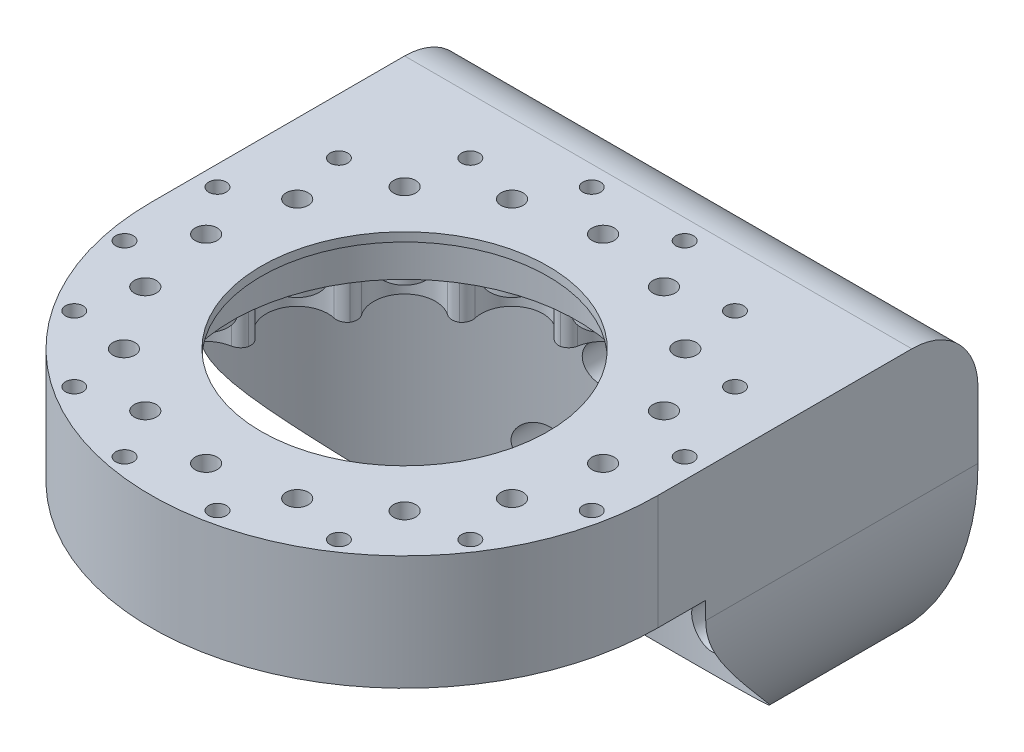
SolidWorks part; units mm, degrees
ref_plane "Front Plane" through (0, 0, 0) normal (0, 0, 1) x (1, 0, 0)
ref_plane "Top Plane" through (0, 0, 0) normal (0, 1, 0) x (1, 0, 0)
ref_plane "Right Plane" through (0, 0, 0) normal (1, 0, 0) x (0, 0, -1)
sketch "Sketch1" plane through (0, 0, 0) normal (0, 1, 0) x (1, 0, 0)
  line L0 (-10.5349, 52.9624) -> (0, 0) construction
  line L1 (0, 0) -> (24.6214, 0) construction
  circle A12 centre (0, 0) radius 39.1
  circle A13 centre (0, 0) radius 57.5
  circle A14 centre (0, 0) radius 54 construction
  circle A15 centre (-10.5349, 52.9624) radius 2
  circle A16 centre (10.5349, 52.9624) radius 2
  circle A17 centre (30.0008, 44.8994) radius 2
  circle A18 centre (44.8994, 30.0008) radius 2
  circle A19 centre (52.9624, 10.5349) radius 2
  circle A20 centre (52.9624, -10.5349) radius 2
  circle A21 centre (44.8994, -30.0008) radius 2
  circle A22 centre (30.0008, -44.8994) radius 2
  circle A23 centre (10.5349, -52.9624) radius 2
  circle A24 centre (-10.5349, -52.9624) radius 2
  circle A25 centre (-30.0008, -44.8994) radius 2
  circle A26 centre (-44.8994, -30.0008) radius 2
  circle A47 centre (-52.9624, -10.5349) radius 2
  circle A48 centre (-52.9624, 10.5349) radius 2
  circle A49 centre (-44.8994, 30.0008) radius 2
  circle A50 centre (-30.0008, 44.8994) radius 2
  point P21 (0, 0)
  point P28 (0, 0)
  point P56 (0, 0)
  point P60 (0, 0)
  dimension "D1" = 101.25
  dimension "D4" = 115
  dimension "D5" = 78.2
  dimension "D6" = 108
  dimension "D7" = 4
  dimension "D8" = 16
extrude "Boss-Extrude1" add sketch "Sketch1" along normal blind 14
sketch "Sketch2" plane through (0, 14, 0) normal (0, 1, 0) x (1, 0, 0)
  circle A0 centre (0, 0) radius 45 construction
  circle A1 centre (0, 45) radius 2.5
  circle A2 centre (17.2208, 41.5746) radius 2.5
  circle A3 centre (31.8198, 31.8198) radius 2.5
  circle A4 centre (41.5746, 17.2208) radius 2.5
  circle A5 centre (45, 0) radius 2.5
  circle A6 centre (41.5746, -17.2208) radius 2.5
  circle A7 centre (31.8198, -31.8198) radius 2.5
  circle A8 centre (17.2208, -41.5746) radius 2.5
  circle A9 centre (0, -45) radius 2.5
  circle A10 centre (-17.2208, -41.5746) radius 2.5
  circle A11 centre (-31.8198, -31.8198) radius 2.5
  circle A12 centre (-41.5746, -17.2208) radius 2.5
  circle A13 centre (-45, 0) radius 2.5
  circle A14 centre (-41.5746, 17.2208) radius 2.5
  circle A15 centre (-31.8198, 31.8198) radius 2.5
  circle A16 centre (-17.2208, 41.5746) radius 2.5
  point P27 (0, 0)
  dimension "D1" = 90
  dimension "D2" = 5
  dimension "D3" = 16
extrude "Cut-Extrude1" cut sketch "Sketch2" against normal blind 40
sketch "Sketch4" plane through (0, 0, 0) normal (0, 1, 0) x (1, 0, 0)
  circle A0 centre (0, 0) radius 45 construction
  circle A1 centre (0, 45) radius 5
  circle A2 centre (0, 45) radius 2.5
  circle A3 centre (17.2208, 41.5746) radius 2.5
  circle A4 centre (31.8198, 31.8198) radius 2.5
  circle A5 centre (41.5746, 17.2208) radius 2.5
  circle A6 centre (45, 0) radius 2.5
  circle A7 centre (41.5746, -17.2208) radius 2.5
  circle A8 centre (31.8198, -31.8198) radius 2.5
  circle A9 centre (17.2208, -41.5746) radius 2.5
  circle A10 centre (0, -45) radius 2.5
  circle A11 centre (-17.2208, -41.5746) radius 2.5
  circle A12 centre (-31.8198, -31.8198) radius 2.5
  circle A13 centre (17.2208, 41.5746) radius 5
  circle A14 centre (31.8198, 31.8198) radius 5
  circle A15 centre (41.5746, 17.2208) radius 5
  circle A16 centre (45, 0) radius 5
  circle A17 centre (41.5746, -17.2208) radius 5
  circle A18 centre (31.8198, -31.8198) radius 5
  circle A19 centre (17.2208, -41.5746) radius 5
  circle A20 centre (0, -45) radius 5
  circle A21 centre (-17.2208, -41.5746) radius 5
  circle A22 centre (-31.8198, -31.8198) radius 5
  circle A23 centre (-41.5746, -17.2208) radius 5
  circle A24 centre (-45, 0) radius 5
  circle A25 centre (-41.5746, 17.2208) radius 5
  circle A26 centre (-31.8198, 31.8198) radius 5
  circle A27 centre (-17.2208, 41.5746) radius 5
  circle A28 centre (-41.5746, -17.2208) radius 2.5
  circle A29 centre (-45, 0) radius 2.5
  circle A30 centre (-41.5746, 17.2208) radius 2.5
  circle A31 centre (-31.8198, 31.8198) radius 2.5
  circle A32 centre (-17.2208, 41.5746) radius 2.5
  point P29 (0, 0)
  point P50 (0, 0)
  dimension "D1" = 10
  dimension "D2" = 16
  dimension "D3" = 16
extrude "Boss-Extrude3" add sketch "Sketch4" against normal blind 1.8
sketch "Sketch5" plane through (0, 0, 0) normal (0, -1, 0) x (1, 0, 0)
  circle A0 centre (0, 0) radius 57.5
  circle A1 centre (0, 0) radius 45
  circle A2 centre (0, 45) radius 7
  circle A3 centre (17.2208, 41.5746) radius 7
  circle A4 centre (31.8198, 31.8198) radius 7
  circle A5 centre (41.5746, 17.2208) radius 7
  circle A6 centre (45, 0) radius 7
  circle A7 centre (41.5746, -17.2208) radius 7
  circle A8 centre (31.8198, -31.8198) radius 7
  circle A9 centre (17.2208, -41.5746) radius 7
  circle A10 centre (0, -45) radius 7
  circle A11 centre (-17.2208, -41.5746) radius 7
  circle A12 centre (-31.8198, -31.8198) radius 7
  circle A13 centre (-41.5746, -17.2208) radius 7
  circle A14 centre (-45, 0) radius 7
  circle A15 centre (-41.5746, 17.2208) radius 7
  circle A16 centre (-31.8198, 31.8198) radius 7
  circle A17 centre (-17.2208, 41.5746) radius 7
  circle A18 centre (0, 0) radius 54 construction
  circle A19 centre (-10.5349, 52.9624) radius 2
  circle A20 centre (10.5349, 52.9624) radius 2
  circle A21 centre (30.0008, 44.8994) radius 2
  circle A22 centre (44.8994, 30.0008) radius 2
  circle A23 centre (52.9624, 10.5349) radius 2
  circle A24 centre (52.9624, -10.5349) radius 2
  circle A25 centre (44.8994, -30.0008) radius 2
  circle A26 centre (30.0008, -44.8994) radius 2
  circle A27 centre (10.5349, -52.9624) radius 2
  circle A28 centre (-10.5349, -52.9624) radius 2
  circle A29 centre (-30.0008, -44.8994) radius 2
  circle A30 centre (-44.8994, -30.0008) radius 2
  circle A31 centre (-52.9624, -10.5349) radius 2
  circle A32 centre (-52.9624, 10.5349) radius 2
  circle A33 centre (-44.8994, 30.0008) radius 2
  circle A34 centre (-30.0008, 44.8994) radius 2
  point P39 (0, 0)
  point P75 (0, 0)
  circle M34 centre (0, 0) radius 57.5
  circle M35 centre (-52.9624, 10.5349) radius 2
  circle M37 centre (-52.9624, -10.5349) radius 2
  circle M39 centre (-30.0008, -44.8994) radius 2
  circle M41 centre (10.5349, -52.9624) radius 2
  circle M43 centre (44.8994, -30.0008) radius 2
  circle M45 centre (52.9624, 10.5349) radius 2
  circle M47 centre (30.0008, 44.8994) radius 2
  circle M49 centre (-10.5349, 52.9624) radius 2
  dimension "D1" = 14
  dimension "D2" = 16
  dimension "D3" = 16
extrude "Boss-Extrude4" add sketch "Sketch5" along normal blind 13 contours A17 A1 A2 A3 A4 A5 A6 A7 A8 A9 A10 A11 A12 A13 A14 A15 A16 M34 M35 M37 M39 M41 M43 M45 M47 M49 region at (-55.8737, 0, 0)
fillet "Fillet2" radius 2.5 32 edges at (-23.46, -6.5, -38.4009) (-26.5001, -6.5, -36.3696) (-6.9788, -6.5, -44.4556) (-10.5648, -6.5, -43.7422) (10.5648, -6.5, -43.7422) (6.9788, -6.5, -44.4556) (26.5001, -6.5, -36.3696) (23.46, -6.5, -38.4009) (38.4009, -6.5, -23.46) (36.3696, -6.5, -26.5001) (44.4556, -6.5, -6.9788) (43.7422, -6.5, -10.5648) (43.7422, -6.5, 10.5648) (44.4556, -6.5, 6.9788) (-38.4009, -6.5, -23.46) (-36.3696, -6.5, -26.5001) (-44.4556, -6.5, -6.9788) (-43.7422, -6.5, -10.5648) (-43.7422, -6.5, 10.5648) (-44.4556, -6.5, 6.9788) (-36.3696, -6.5, 26.5001) (-38.4009, -6.5, 23.46) (-23.46, -6.5, 38.4009) (-26.5001, -6.5, 36.3696) (-10.5648, -6.5, 43.7422) (-6.9788, -6.5, 44.4556) (6.9788, -6.5, 44.4556) (10.5648, -6.5, 43.7422) (23.46, -6.5, 38.4009) (26.5001, -6.5, 36.3696) (38.4009, -6.5, 23.46) (36.3696, -6.5, 26.5001)
sketch "Sketch6" plane through (0, -13, 0) normal (0, -1, 0) x (1, 0, 0)
  line L0 (-57.5, 0) -> (57.5, 0) construction
  line L1 (57.5, 0) -> (57.5, -57.5)
  line L2 (57.5, -57.5) -> (-57.5, -57.5)
  line L3 (-57.5, -57.5) -> (-57.5, 0)
  circle A0 centre (0, 0) radius 57.5 construction
  arc A1 (-57.5, 0) -> (57.5, 0) centre (0, 0) ccw
extrude "Boss-Extrude7" add sketch "Sketch6" against normal blind 27 contours A1 L2 L1 | A1 L3 L2 region at (-44.6563, -13, -44.6563) region at (44.6563, -13, -44.6563)
sketch "Sketch7" plane through (-57.5, 0, 0) normal (-1, 0, 0) x (0, 0, 1)
  line L0 (-57.5, 14) -> (-57.5, -73.5)
  line L1 (-57.5, -73.5) -> (-72.5, -73.5)
  line L2 (-72.5, -73.5) -> (-72.5, 14)
  line L3 (-72.5, 14) -> (-57.5, 14)
  line L4 (-57.5, -73.5) -> (0, -13)
  line L5 (0, -13) -> (-57.5, -13)
  line M5 (-57.5, -13) -> (0, -13)
  line M8 (-57.5, 14) -> (-57.5, -13)
  dimension "D1" = 15
  dimension "D2" = 87.5
  dimension "D3" = 60.5
extrude "Boss-Extrude8" add sketch "Sketch7" against normal blind 115 contours L3 L2 L1 L0 M8 | L0 L4 M5 region at (-57.5, -29.75, -65) region at (-57.5, -33.1667, -38.3333)
sketch "Sketch8" plane through (0, -73.5, 0) normal (0, -1, 0) x (1, 0, 0)
  circle A0 centre (0, 0) radius 58.5
  dimension "D1" = 117
extrude "Cut-Extrude2" cut sketch "Sketch8" against normal blind 61.5
sketch "Sketch9" plane through (0, 0, -72.5) normal (0, 0, -1) x (-1, 0, 0)
  line L0 (0, 19.2611) -> (0, -105.8991) construction
  line L1 (-57.5, -73.5) -> (57.5, -73.5) construction
  circle A0 centre (0, -43.5) radius 30 construction
  circle A1 centre (0, -43.5) radius 23 construction
  circle A2 centre (23, -43.5) radius 2.25
  circle A3 centre (11.5, -63.4186) radius 2.25
  circle A4 centre (-11.5, -63.4186) radius 2.25
  circle A5 centre (-23, -43.5) radius 2.25
  circle A6 centre (-11.5, -23.5814) radius 2.25
  circle A7 centre (11.5, -23.5814) radius 2.25
  point P22 (0, -43.5)
  dimension "D1" = 60
  dimension "D2" = 46
  dimension "D3" = 4.5
  dimension "D4" = 6
extrude "Cut-Extrude3" cut sketch "Sketch9" against normal blind 67.5
sketch "Sketch10" plane through (0, 0, 0) normal (0, 0, 1) x (1, 0, 0)
  line L0 (57.5, -73.5) -> (10.7703, -73.5) construction
  circle A0 centre (0, -43.5) radius 30 construction
  circle A1 centre (0, -43.5) radius 23 construction
  circle A2 centre (23, -43.5) radius 4.5
  circle A3 centre (11.5, -63.4186) radius 4.5
  circle A4 centre (-11.5, -63.4186) radius 4.5
  circle A5 centre (-23, -43.5) radius 4.5
  circle A6 centre (-11.5, -23.5814) radius 4.5
  circle A7 centre (11.5, -23.5814) radius 4.5
  point P19 (0, -43.5)
  dimension "D1" = 60
  dimension "D2" = 46
  dimension "D3" = 9
  dimension "D4" = 6
extrude "Cut-Extrude4" cut sketch "Sketch10" against normal blind 62.5
sketch "Sketch11" plane through (0, 0, -72.5) normal (0, 0, -1) x (-1, 0, 0)
  line L0 (0, 13.9005) -> (0, -82.4311) construction
  line L1 (-57.5, -73.5) -> (57.5, -73.5) construction
  line L2 (-57.5, -16) -> (-57.5, -73.5)
  line L3 (-57.5, -73.5) -> (57.5, -73.5)
  line L4 (57.5, -73.5) -> (57.5, -20.06)
  circle A0 centre (0, -16) radius 57.5
  line M8 (57.5, -73.5) -> (57.5, 14)
  line M10 (-57.5, 14) -> (-57.5, -73.5)
  line M11 (-57.5, -73.5) -> (57.5, -73.5)
  dimension "D1" = 115
extrude "Cut-Extrude5" cut sketch "Sketch11" against normal blind 133 contours A0 M10 M11 | A0 L3 M8 region at (44.6563, -60.6563, -72.5) region at (-44.6563, -60.6563, -72.5)
fillet "Fillet4" radius 15 1 edges at (0, 14, -72.5)
sketch "Sketch12" plane through (0, 14, 0) normal (0, 1, 0) x (1, 0, 0)
  circle A0 centre (0, 0) radius 39.1
  circle A1 centre (0, 0) radius 32.5
  dimension "D1" = 65
extrude "Boss-Extrude9" add sketch "Sketch12" against normal blind 2
